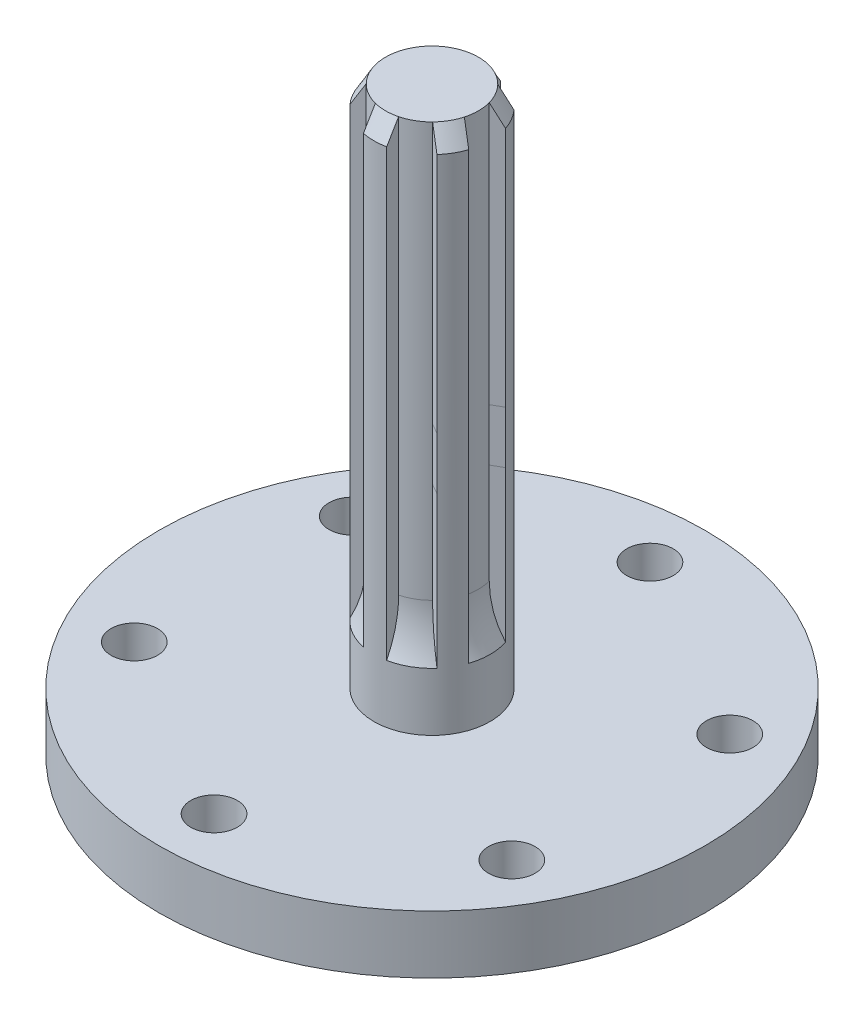
SolidWorks part; units mm, degrees
material "AISI 4340 Steel, normalized"
ref_plane "Front Plane" through (0, 0, 0) normal (0, 0, 1) x (1, 0, 0)
ref_plane "Top Plane" through (0, 0, 0) normal (0, 1, 0) x (1, 0, 0)
ref_plane "Right Plane" through (0, 0, 0) normal (1, 0, 0) x (0, 0, -1)
sketch "Sketch1" plane through (0, 0, 0) normal (0, 1, 0) x (1, 0, 0)
  circle A0 centre (0, 0) radius 46.99
  circle A2 centre (0, 37.5) radius 4
  circle A3 centre (32.476, 18.75) radius 4
  circle A4 centre (32.476, -18.75) radius 4
  circle A5 centre (0, -37.5) radius 4
  circle A6 centre (-32.476, -18.75) radius 4
  circle A7 centre (-32.476, 18.75) radius 4
  circle A8 centre (0, 0) radius 8.509
  point P19 (0, 0)
  dimension "D1" = 93.98
  dimension "D2" = 17.018
  dimension "D3" = 8
  dimension "D4" = 6
extrude "Boss-Extrude1" add sketch "Sketch1" along normal blind 10 contours A0 A8 A7 A6 A5 A4 A3 A2 | A8 region at (-45.6609, 0, 0) region at (0, 0, 0)
fillet "Fillet1" [suppressed] radius 0.5
ref_axis "Axis1" through (0, 136.434, 0) along (0, -1, 0)
sketch "Sketch2" plane through (0, 10, 0) normal (0, 1, 0) x (1, 0, 0)
  line L0 (-16.3205, 11.7321) -> (18.3205, -8.2679)
  line L1 (2, -20) -> (-2, -20)
  line L2 (2, -20) -> (2, 20)
  line L3 (2, 20) -> (-2, 20)
  line L4 (-2, -20) -> (-2, 20)
  line L5 (2, -20) -> (-2, 20) construction
  line L6 (2, 20) -> (-2, -20) construction
  line L7 (16.3205, -11.7321) -> (18.3205, -8.2679)
  line L8 (-18.3205, 8.2679) -> (16.3205, -11.7321)
  line L9 (-18.3205, 8.2679) -> (-16.3205, 11.7321)
  line L10 (18.3205, 8.2679) -> (-16.3205, -11.7321)
  line L11 (-18.3205, -8.2679) -> (-16.3205, -11.7321)
  line L12 (16.3205, 11.7321) -> (-18.3205, -8.2679)
  line L13 (16.3205, 11.7321) -> (18.3205, 8.2679)
  circle A0 centre (0, 0) radius 8
  circle A1 centre (0, 0) radius 10
  point P18 (0, 0)
  dimension "D1" = 16
  dimension "D5" = 20
  dimension "D2" = 40
  dimension "D3" = 4
  dimension "D4" = 3
extrude "Boss-Extrude2" add sketch "Sketch2" along normal blind 90 contours L0 A0 L8 L12 L4 | A0 L0 L9 L8 | L4 A0 L0 | L2 A0 L4 L0 L12 | A0 L2 L3 L4 | L12 A0 L2 | A0 L10 L13 L12 | L0 A0 L10 | L8 A0 L0 L10 L2 | A0 L8 L7 L0 | L4 A0 L2 L8 L10 | L2 A0 L8 | L12 A0 L10 L4 L8 | A0 L4 L1 L2 | L10 L8 L4 | L2 L10 L8 | L4 L12 L8 | L10 L0 L2 | L2 L12 L0 | L12 L0 L4 | L8 A0 L12 | L10 A0 L4 | L0 L12 L4 L8 L10 L2 | L10 A0 L12 L2 L0 | A0 L12 L11 L10 region at (-7.7283, 10, -4.4619) region at (-3.3005, 10, -5.7167) region at (-4.6686, 10, -2.6954) region at (0, 10, -8.9239) region at (0, 10, -5.3908) region at (-1.3333, 10, -2.3094) region at (-6.601, 10, 0) region at (-7.7283, 10, 4.4619) region at (1.3333, 10, -2.3094) region at (0, 10, 0) region at (-2.6667, 10, 0) region at (3.3005, 10, -5.7167) region at (-4.6686, 10, 2.6954) region at (7.7283, 10, -4.4619) region at (4.6686, 10, -2.6954) region at (2.6667, 10, 0) region at (-1.3333, 10, 2.3094) region at (-3.3005, 10, 5.7167) region at (0, 10, 8.9239) region at (6.601, 10, 0) region at (4.6686, 10, 2.6954) region at (1.3333, 10, 2.3094) region at (0, 10, 5.3908) region at (7.7283, 10, 4.4619) region at (3.3005, 10, 5.7167)
sketch "Sketch4" plane through (0, 10, 0) normal (0, 1, 0) x (1, 0, 0)
  circle A0 centre (0, 0) radius 10
  arc A1 (2, 9.798) -> (-2, 9.798) centre (0, 0) ccw construction
extrude "Boss-Extrude3" add sketch "Sketch4" along normal blind 10
fillet "Fillet2" radius 20 6 edges at (4, 20, 6.9282) (-4, 20, 6.9282) (-8, 20, 0) (-4, 20, -6.9282) (4, 20, -6.9282) (8, 20, 0)
sketch "Sketch5" plane through (0, 0, 0) normal (0, 0, 1) x (1, 0, 0)
  circle A0 centre (29.9802, 28.7178) radius 22.272 construction
  spline S0 degree 3 poles (9.4853, 20) (8.9031, 21.3599) (8.4635, 22.7689) (8.0146, 24.9549) (7.9004, 25.696) (7.7467, 27.203) (7.7082, 27.9591) (7.7082, 28.7178) knots 0 0 0 0 0.5 0.5 0.75 0.75 1 1 1 1 construction
ref_plane "Plane1" through (0, 55, 0) normal (0, 1, 0) x (1, 0, 0)
ref_plane "Plane2" through (0, 46, 0) normal (0, 1, 0) x (1, 0, 0)
split line "Split Line3"
split line "Split Line4"
sketch "Sketch8" plane through (0, 100, 0) normal (0, 1, 0) x (1, 0, 0)
  circle A0 centre (0, 0) radius 8
sketch "Sketch7" plane through (0, 0, 0) normal (1, 0, 0) x (0, 0, -1)
  line L2 (10, 100) -> (10, 96.5359)
  line L3 (10, 10) -> (10, 100) construction
  line L5 (10, 96.5359) -> (8, 100)
  line L7 (8, 100) -> (10, 100)
  line L13 (8, 100) -> (-8, 100) construction
  dimension "D1" = 30
revolve "Cut-Revolve1" cut sketch "Sketch7" angle 360 about axis through (0, 136.434, 0) along (0, -1, 0)
